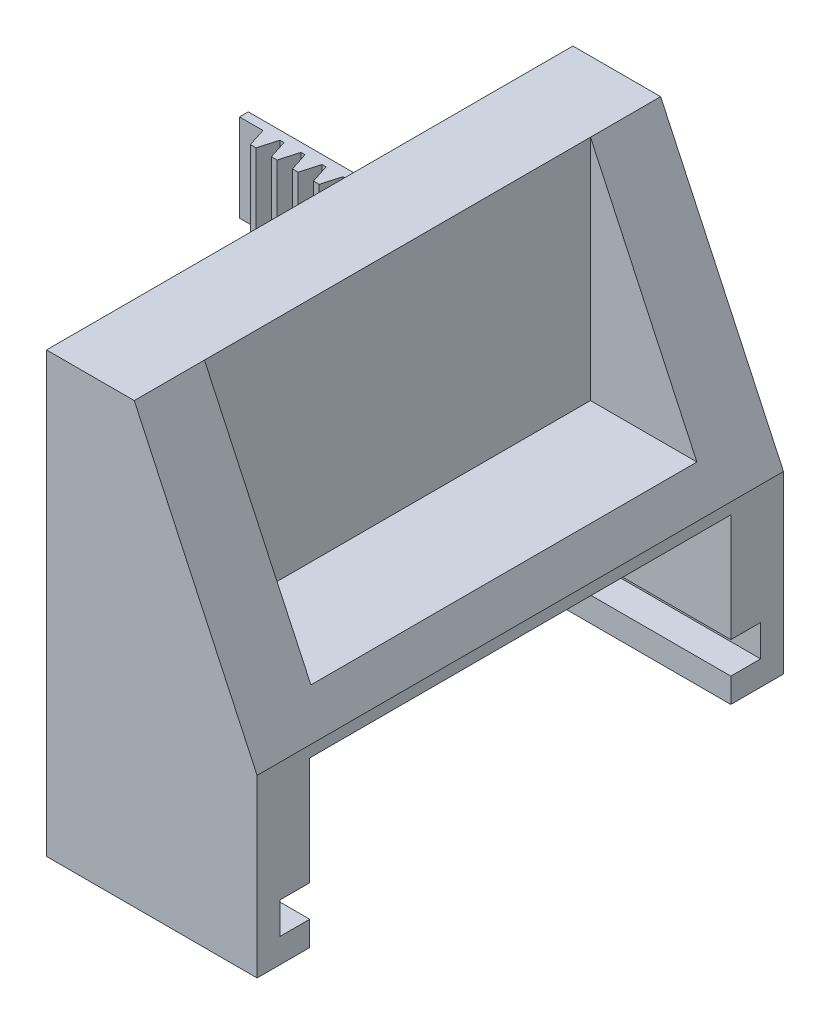
SolidWorks part; units mm, degrees
ref_plane "Front Plane" through (0, 0, 0) normal (0, 0, 1) x (1, 0, 0)
ref_plane "Top Plane" through (0, 0, 0) normal (0, 1, 0) x (1, 0, 0)
ref_plane "Right Plane" through (0, 0, 0) normal (1, 0, 0) x (0, 0, -1)
sketch "Sketch1" plane through (0, 0, 0) normal (0, 0, 1) x (1, 0, 0)
  line L0 (0, 0) -> (0, -25)
  line L1 (0, -25) -> (12, -25)
  line L2 (12, -25) -> (12, -15)
  line L3 (12, -15) -> (5, 0)
  line L4 (5, 0) -> (0, 0)
  dimension "D1" = 25
  dimension "D2" = 12
  dimension "D3" = 10
  dimension "D4" = 5
extrude "Boss-Extrude1" add sketch "Sketch1" against normal blind 30
sketch "Sketch4" plane through (0, 0, 0) normal (-1, 0, 0) x (0, 0, 1)
  line L0 (-30, 0) -> (-30, -25) construction
  line L1 (-27, -15.6386) -> (-3, -15.6386)
  line L2 (-27, -15.6386) -> (-27, -29.6386)
  line L3 (-27, -29.6386) -> (-3, -29.6386)
  line L4 (-3, -15.6386) -> (-3, -29.6386)
  point P4 (-27, -22.6386)
  dimension "D1" = 24
  dimension "D2" = 14
  dimension "D3" = 3
extrude "Cut-Extrude2" cut sketch "Sketch4" against normal blind 25 contours L2 L1 L4 L3
sketch "Sketch5" plane through (0, 0, 0) normal (-1, 0, 0) x (0, 0, 1)
  line L0 (-3, -15.6386) -> (-3, -25) construction
  line L1 (-3, -21.8) -> (-1.3, -21.8)
  line L2 (-3, -21.8) -> (-3, -23.6)
  line L3 (-3, -23.6) -> (-1.3, -23.6)
  line L4 (-1.3, -21.8) -> (-1.3, -23.6)
  line L5 (-3, -25) -> (0, -25) construction
  dimension "D1" = 1.8
  dimension "D2" = 1.7
  dimension "D3" = 1.4
extrude "Cut-Extrude3" cut sketch "Sketch5" against normal blind 15
ref_plane "Plane1" through (0, 0, -15) normal (0, 0, 1) x (1, 0, 0)
mirror "Mirror1" about plane through (0, 0, -15) normal (0, 0, 1) of "Cut-Extrude3"
sketch "Sketch6" plane through (0, 0, -15) normal (0, 0, 1) x (1, 0, 0)
  line L0 (5, 0) -> (5, -13)
  line L1 (5, -13) -> (11.0667, -13)
  line L2 (12, -15) -> (5, 0) construction
  line L3 (11.0667, -13) -> (5, 0)
  dimension "D1" = 13
extrude "Cut-Extrude4" cut sketch "Sketch6" against normal mid plane 22
ref_plane "Plane2" through (0, -15, 0) normal (0, 1, 0) x (1, 0, 0)
sketch "Sketch7" plane through (0, -15, 0) normal (0, 1, 0) x (1, 0, 0)
  line L0 (0, 27.5) -> (-16, 27.5)
  line L1 (0, 30) -> (0, 0) construction
  line L3 (0, 27.5) -> (0, 27)
  line L4 (0, 27) -> (-0.5, 27)
  line L47 (-0.5, 27) -> (-0.8043, 25.9435)
  line L62 (-13.75, 15) -> (13.75, 15) construction
  line L63 (-0.8043, 25.9435) -> (-1.1273, 25.9435)
  line L64 (-1.1273, 25.9435) -> (-1.4655, 27)
  line L65 (-2.3273, 25.9435) -> (-2.6655, 27)
  line L66 (-2.0043, 25.9435) -> (-2.3273, 25.9435)
  line L67 (-1.7, 27) -> (-2.0043, 25.9435)
  line L68 (-3.5273, 25.9435) -> (-3.8655, 27)
  line L69 (-3.2043, 25.9435) -> (-3.5273, 25.9435)
  line L70 (-2.9, 27) -> (-3.2043, 25.9435)
  line L71 (-4.7273, 25.9435) -> (-5.0655, 27)
  line L72 (-4.4043, 25.9435) -> (-4.7273, 25.9435)
  line L73 (-4.1, 27) -> (-4.4043, 25.9435)
  line L74 (-5.9273, 25.9435) -> (-6.2655, 27)
  line L75 (-5.6043, 25.9435) -> (-5.9273, 25.9435)
  line L76 (-5.3, 27) -> (-5.6043, 25.9435)
  line L77 (-7.1273, 25.9435) -> (-7.4655, 27)
  line L78 (-6.8043, 25.9435) -> (-7.1273, 25.9435)
  line L79 (-6.5, 27) -> (-6.8043, 25.9435)
  line L80 (-8.3273, 25.9435) -> (-8.6655, 27)
  line L81 (-8.0043, 25.9435) -> (-8.3273, 25.9435)
  line L82 (-7.7, 27) -> (-8.0043, 25.9435)
  line L83 (-9.5273, 25.9435) -> (-9.8655, 27)
  line L84 (-9.2043, 25.9435) -> (-9.5273, 25.9435)
  line L85 (-8.9, 27) -> (-9.2043, 25.9435)
  line L86 (-10.7273, 25.9435) -> (-11.0655, 27)
  line L87 (-10.4043, 25.9435) -> (-10.7273, 25.9435)
  line L88 (-10.1, 27) -> (-10.4043, 25.9435)
  line L89 (-11.9273, 25.9435) -> (-12.2655, 27)
  line L90 (-11.6043, 25.9435) -> (-11.9273, 25.9435)
  line L91 (-11.3, 27) -> (-11.6043, 25.9435)
  line L92 (-13.1273, 25.9435) -> (-13.4655, 27)
  line L93 (-12.8043, 25.9435) -> (-13.1273, 25.9435)
  line L94 (-12.5, 27) -> (-12.8043, 25.9435)
  line L95 (-14.3273, 25.9435) -> (-14.6655, 27)
  line L96 (-14.0043, 25.9435) -> (-14.3273, 25.9435)
  line L97 (-13.7, 27) -> (-14.0043, 25.9435)
  line L98 (-1.4655, 27) -> (-1.7, 27)
  line L99 (-2.6655, 27) -> (-2.9, 27)
  line L100 (-3.8655, 27) -> (-4.1, 27)
  line L101 (-5.0655, 27) -> (-5.3, 27)
  line L102 (-6.2655, 27) -> (-6.5, 27)
  line L103 (-7.4655, 27) -> (-7.7, 27)
  line L104 (-8.6655, 27) -> (-8.9, 27)
  line L105 (-9.8655, 27) -> (-10.1, 27)
  line L106 (-11.0655, 27) -> (-11.3, 27)
  line L107 (-14.9, 27) -> (-16, 27)
  line L108 (-16, 27) -> (-16, 27.5)
  line L109 (-12.2655, 27) -> (-12.5, 27)
  line L110 (-13.4655, 27) -> (-13.7, 27)
  line L111 (-14.6655, 27) -> (-14.9, 27)
  point P9 (0, 0)
  point P55 (0, 0)
  point P56 (0, 0)
  dimension "D1" = 12
  dimension "D2" = 16
  dimension "D3" = 0.5
  dimension "D6" = 0.5
  dimension "D7" = 12.5
extrude "Boss-Extrude2" add sketch "Sketch7" along normal blind 5
